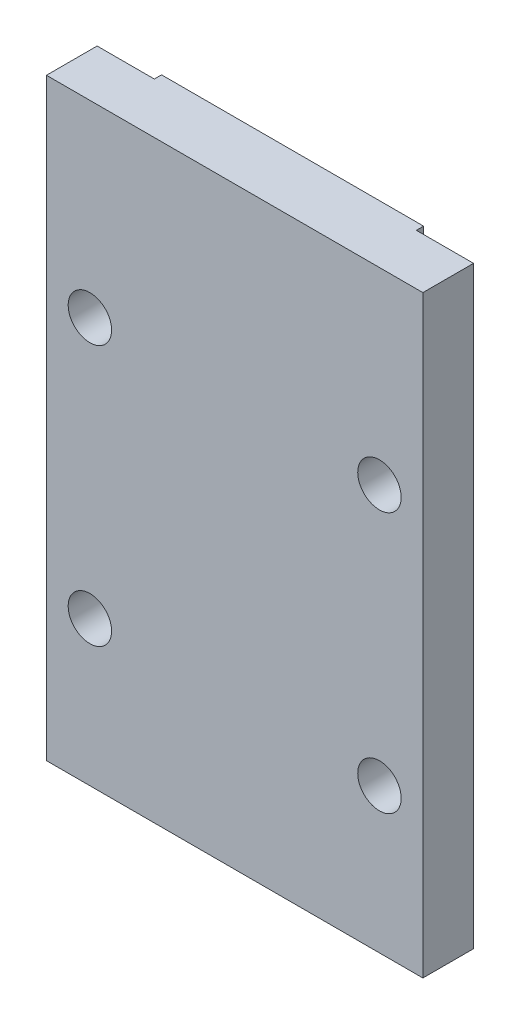
SolidWorks part; units mm, degrees
ref_plane "Front Plane" through (0, 0, 0) normal (0, 0, 1) x (1, 0, 0)
ref_plane "Top Plane" through (0, 0, 0) normal (0, 1, 0) x (1, 0, 0)
ref_plane "Right Plane" through (0, 0, 0) normal (1, 0, 0) x (0, 0, -1)
sketch "Sketch1" plane through (0, 0, 0) normal (0, 0, 1) x (1, 0, 0)
  line L8 (0, 0) -> (0, 41) construction
  line L9 (0, 41) -> (3.95, 41) construction
  line L10 (3.95, 41) -> (3.95, 31) construction
  line L11 (3.95, 31) -> (10.3, 31) construction
  line L12 (10.3, 31) -> (10.3, 9) construction
  line L13 (10.3, 9) -> (8.55, 9) construction
  line L14 (8.55, 9) -> (8.55, 4) construction
  line L15 (8.55, 4) -> (13, 4) construction
  line L16 (13, 4) -> (13, 0) construction
  line L17 (13, 0) -> (0, 0) construction
  line L18 (0, 0) -> (0, 41)
  line L19 (0, 41) -> (26, 41)
  line L20 (26, 41) -> (26, 0)
  line L21 (26, 0) -> (0, 0)
  line L22 (3, 41) -> (3, 0) construction
  line L23 (13, 41) -> (13, 0) construction
  circle A1 centre (3, 28) radius 1.5
  circle A2 centre (3, 10) radius 1.5
  circle A3 centre (23, 10) radius 1.5
  circle A4 centre (23, 28) radius 1.5
  dimension "D13" = 3
  dimension "D15" = 10
  dimension "D1" = 10
  dimension "D2" = 41
  dimension "D3" = 4
  dimension "D4" = 10.3
  dimension "D5" = 13
  dimension "D6" = 9.05
  dimension "D7" = 5
  dimension "D8" = 1.75
  dimension "D9" = 26
  dimension "D14" = 3
  dimension "D16" = 13
extrude "Boss-Extrude1" add sketch "Sketch1" along normal blind 4
sketch "Sketch3" plane through (0, 0, 0) normal (0, 0, -1) x (-1, 0, 0)
  line L0 (-3.95, 41) -> (-22.05, 41)
  line L1 (-17.45, 9) -> (-17.45, 4)
  line L2 (-3.95, 41) -> (-3.95, 31)
  line L3 (-3.95, 31) -> (-10.3, 31)
  line L4 (-10.3, 28) -> (-10.3, 12)
  line L5 (-10.3, 9) -> (-8.55, 9)
  line L6 (-8.55, 9) -> (-8.55, 4)
  line L7 (-8.55, 4) -> (-17.45, 4)
  line L8 (-13, 41) -> (-13, 0) construction
  line L9 (-15.7, 9) -> (-17.45, 9)
  line L10 (-15.7, 28) -> (-15.7, 12)
  line L11 (-22.05, 31) -> (-15.7, 31)
  line L12 (-22.05, 41) -> (-22.05, 31)
  arc A0 (-10.3, 31) -> (-10.3, 28) centre (-10.3, 29.5) ccw
  arc A1 (-10.3, 9) -> (-10.3, 12) centre (-10.3, 10.5) cw
  arc A2 (-15.7, 9) -> (-15.7, 12) centre (-15.7, 10.5) ccw
  arc A3 (-15.7, 31) -> (-15.7, 28) centre (-15.7, 29.5) cw
  point P29 (-13, 4)
extrude "Cut-Extrude1" cut sketch "Sketch3" against normal blind 0.5 flip side to cut
